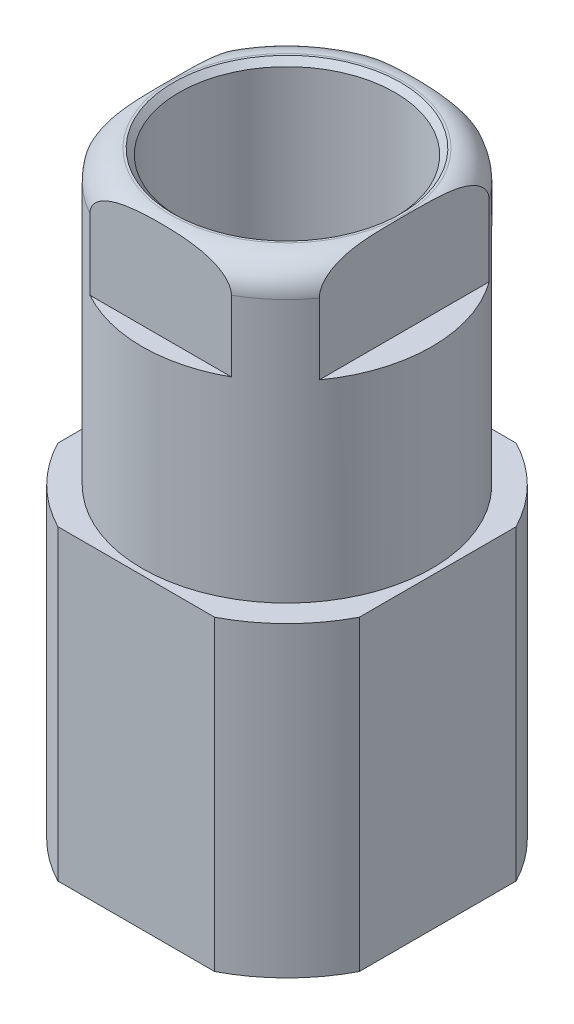
SolidWorks part; units mm, degrees
ref_plane "Front Plane" through (0, 0, 0) normal (0, 0, 1) x (1, 0, 0)
ref_plane "Top Plane" through (0, 0, 0) normal (0, 1, 0) x (1, 0, 0)
ref_plane "Right Plane" through (0, 0, 0) normal (1, 0, 0) x (0, 0, -1)
sketch "Sketch1" plane through (0, 0, 0) normal (0, 1, 0) x (1, 0, 0)
  line L0 (-8.375, 0) -> (-8.375, -8.375)
  line L2 (0, -8.375) -> (-15.295, -8.375)
  line L5 (8.375, 0) -> (8.375, 10.9003)
  line L7 (0, 8.375) -> (8.375, 8.375)
  line L10 (-8.375, -8.375) -> (8.375, -8.375)
  line L11 (-8.375, -8.375) -> (-8.375, 8.375)
  line L12 (-8.375, 8.375) -> (8.375, 8.375)
  line L13 (8.375, -8.375) -> (8.375, 8.375)
  circle A0 centre (0, 0) radius 8.375
  dimension "D1" = 16.75
extrude "Boss-Extrude2" add sketch "Sketch1" along normal blind 17.05 contours L11 L10 L13 L12
sketch "Sketch3" plane through (0, 0, 0) normal (0, -1, 0) x (1, 0, 0)
  circle A0 centre (0, 0) radius 9.44
  dimension "D1" = 18.88
extrude "Cut-Extrude1" cut sketch "Sketch3" against normal blind 17.05 flip side to cut contours A0
sketch "Sketch4" plane through (0, 17.05, 0) normal (0, 1, 0) x (1, 0, 0)
  circle A0 centre (0, 0) radius 8.045
  dimension "D1" = 16.09
extrude "Boss-Extrude3" add sketch "Sketch4" along normal blind 16.2
fillet "Fillet1" radius 1.6 1 edges at (0, 33.25, 8.045)
sketch "Sketch6" plane through (0, 33.25, 0) normal (0, 1, 0) x (1, 0, 0)
  line L5 (-6.515, 7.02) -> (6.515, 7.02)
  line L6 (-6.515, 7.02) -> (-6.515, -7.02)
  line L7 (-6.515, -7.02) -> (6.515, -7.02)
  line L8 (6.515, 7.02) -> (6.515, -7.02)
  dimension "D1" = 13.03
  dimension "D2" = 14.04
extrude "Cut-Extrude2" cut sketch "Sketch6" against normal blind 5.53 flip side to cut
sketch "Sketch8" plane through (0, 33.25, 0) normal (0, 1, 0) x (1, 0, 0)
  circle A0 centre (0, 0) radius 6
  dimension "D1" = 12
extrude "Cut-Extrude3" cut sketch "Sketch8" against normal blind 12.7 contours A0
chamfer "Chamfer5" distance 0.32 angle 45 1 edges at (0, 33.25, 6)
sketch "Sketch20" plane through (0, 20.55, 0) normal (0, 1, 0) x (1, 0, 0)
  point P0 (0, 0)
hole_wizard "M10 Clearance Hole2" positions "Sketch20" profile "Sketch21" hole size "M10" standard "ANSI Metric"
sketch "Sketch21" plane through (0, 20.55, 0) normal (1, 0, 0) x (0, 0, 1)
  line L0 (0, 0) -> (0, 12.08)
  line L1 (0, 12.08) -> (5.5, 8.7753)
  line L2 (5.5, 8.7753) -> (5.5, 0)
  line L5 (5.5, 0) -> (0, 0)
  line L10 (0, 12.08) -> (-5.5, 8.7753) construction
  line L11 (0, -6.35) -> (0, 107.95) construction
  dimension "Hole Dia." = 11
  dimension "Hole Depth" = 12.08
  dimension "Drill Angle" = 118
chamfer "Chamfer7" distance 1 angle 45 1 edges at (0, 20.55, 5.5)
thread "Thread2" pitch 1 method cut profile "Thread Profile2" start angle 0, offset 0, length 0, pitch 1, diameter 11
ref_plane "Plane8" through (-5.5, 19.55, 0) normal (0, 0, 1) x (-1, 0, 0)
sketch "Thread Profile2" plane through (-5.5, 19.55, 0) normal (0, 0, 1) x (-1, 0, 0)
  line L0 (0, 0) -> (0, 1) construction
  line L1 (0, 0) -> (0.5413, 0.3125)
  line L2 (0.5413, 0.3125) -> (0.5413, 0.4375)
  line L3 (0.5413, 0.4375) -> (0, 0.75)
  line L4 (0.5413, 0.375) -> (0, 0.375) construction
  line L11 (0, 0) -> (0, 0.75)
  point P2 (0, 0)
  dimension "Pitch" = 1
  dimension "Profile_Angle" = 60
  dimension "Profile_Land" = 0.125
  dimension "Profile_Height" = 0.5413
